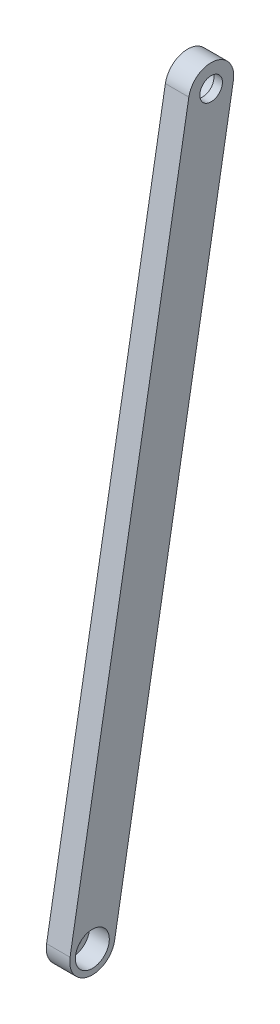
SolidWorks part; units mm, degrees
note: The reader was unsure of these and kept them because the rebuilt part matched: shared geometry of "Sketch2<3>", "Sketch2<4>", "Sketch2<5>".
material "5052-H32"
ref_plane "Front Plane" through (0, 0, 0) normal (0, 0, 1) x (1, 0, 0)
ref_plane "Top Plane" through (0, 0, 0) normal (0, 1, 0) x (1, 0, 0)
ref_plane "Right Plane" through (0, 0, 0) normal (1, 0, 0) x (0, 0, -1)
sketch "Sketch2" plane through (0, 0, 0) normal (1, 0, 0) x (0, 0, -1)
  line L0 (24.9413, 120.5171) -> (3.9413, -0.6829)
  line L1 (-3.9413, 0.6829) -> (17.0587, 121.8829)
  arc A0 (24.9413, 120.5171) -> (17.0587, 121.8829) centre (21, 121.2) ccw
  circle A1 centre (21, 121.2) radius 4 construction
  arc A2 (3.9413, -0.6829) -> (-3.9413, 0.6829) centre (0, 0) cw
  circle A3 centre (21, 121.2) radius 3
  circle A4 centre (21, 121.2) radius 3 construction
  circle A5 centre (21, 121.2) radius 2
  circle A6 centre (21, 121.2) radius 2 construction
  circle A7 centre (0, 0) radius 3
  circle A8 centre (0, 0) radius 3 construction
  circle A11 centre (0, 0) radius 2 construction
  circle A12 centre (0, 0) radius 2
extrude "Boss-Extrude1" add sketch "Sketch2" against normal up to vertex (15.5 mm away) from vertex at -11.35
extrude "Cut-Extrude1" cut sketch "Sketch2<3>" along normal up to vertex from vertex contours A3 A5 | A5
sketch "Sketch2<3>" plane through (0, 0, 0) normal (1, 0, 0) x (0, 0, -1) same geometry as "Sketch2"
extrude "Cut-Extrude2" cut sketch "Sketch2<4>" along normal up to vertex from vertex contours A5
sketch "Sketch2<4>" plane through (0, 0, 0) normal (1, 0, 0) x (0, 0, -1) same geometry as "Sketch2"
extrude "Cut-Extrude3" cut sketch "Sketch2<5>" against normal up to vertex from vertex
sketch "Sketch2<5>" plane through (0, 0, 0) normal (1, 0, 0) x (0, 0, -1) same geometry as "Sketch2"
ref_plane "Plane1" through (-15.5, 0, 0) normal (-1, 0, 0) x (0, 0, 1)
mirror "Mirror1" [suppressed] about plane through (-15.5, 0, 0) normal (-1, 0, 0)
other "Intersect1" [suppressed]
delete or keep bodies "Body-Delete/Keep 1" [suppressed] type delete bodies bodies 108
